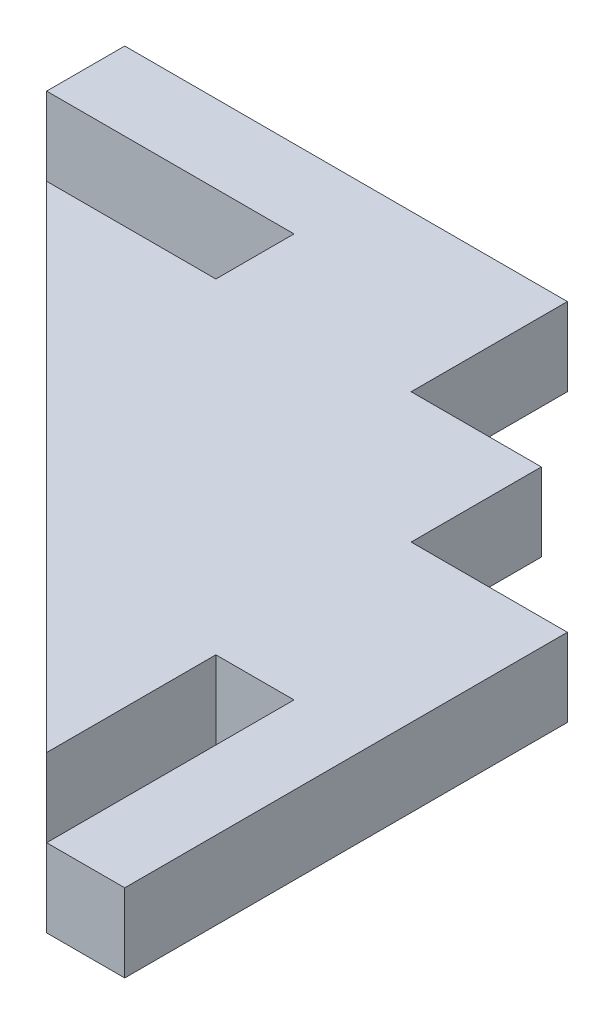
SolidWorks part; units mm, degrees
ref_plane "Front" through (0, 0, 0) normal (0, 0, 1) x (1, 0, 0)
ref_plane "Top" through (0, 0, 0) normal (0, 1, 0) x (1, 0, 0)
ref_plane "Right" through (0, 0, 0) normal (1, 0, 0) x (0, 0, -1)
sketch "Sketch2" plane through (0, 0, 0) normal (0, 1, 0) x (1, 0, 0)
  line L0 (0, 0) -> (-10, 0)
  line L1 (-50, 12) -> (12, -50)
  line L2 (0, -10) -> (0, 0)
  line L3 (-10, 0) -> (-10, 12)
  line L4 (-10, 12) -> (-50, 12)
  line L7 (12, -50) -> (12, -10)
  line L8 (12, -10) -> (0, -10)
  dimension "D1" = 12
  dimension "D3" = 50
  dimension "D4" = 10
extrude "Boss-Extrude1" add sketch "Sketch2" along normal blind 6
sketch "Sketch3" plane through (0, 6, 0) normal (0, 1, 0) x (1, 0, 0)
  line L0 (-50, 12) -> (12, -50) construction
  line L1 (-44, 6) -> (-25, 6)
  line L2 (-44, 6) -> (-44, 0)
  line L3 (-44, 0) -> (-25, 0)
  line L4 (-25, 6) -> (-25, 0)
  line L5 (0, 0) -> (-10, 0) construction
  line L6 (6, -44) -> (0, -44)
  line L7 (6, -44) -> (6, -25)
  line L8 (6, -25) -> (0, -25)
  line L9 (0, -44) -> (0, -25)
  line L10 (0, -10) -> (0, 0) construction
  dimension "D1" = 6
  dimension "D2" = 25
extrude "Cut-Extrude1" cut sketch "Sketch3" against normal through all
sketch "Sketch4" plane through (0, 6, 0) normal (0, 1, 0) x (1, 0, 0)
  line L1 (-44, 6) -> (-50, 6)
  line L2 (-44, 6) -> (-44, 12)
  line L3 (-44, 12) -> (-50, 12)
  line L4 (-50, 6) -> (-50, 12)
  line L5 (6, -44) -> (12, -44)
  line L6 (6, -44) -> (6, -50)
  line L7 (6, -50) -> (12, -50)
  line L8 (12, -44) -> (12, -50)
extrude "Cut-Extrude2" cut sketch "Sketch4" against normal through all
